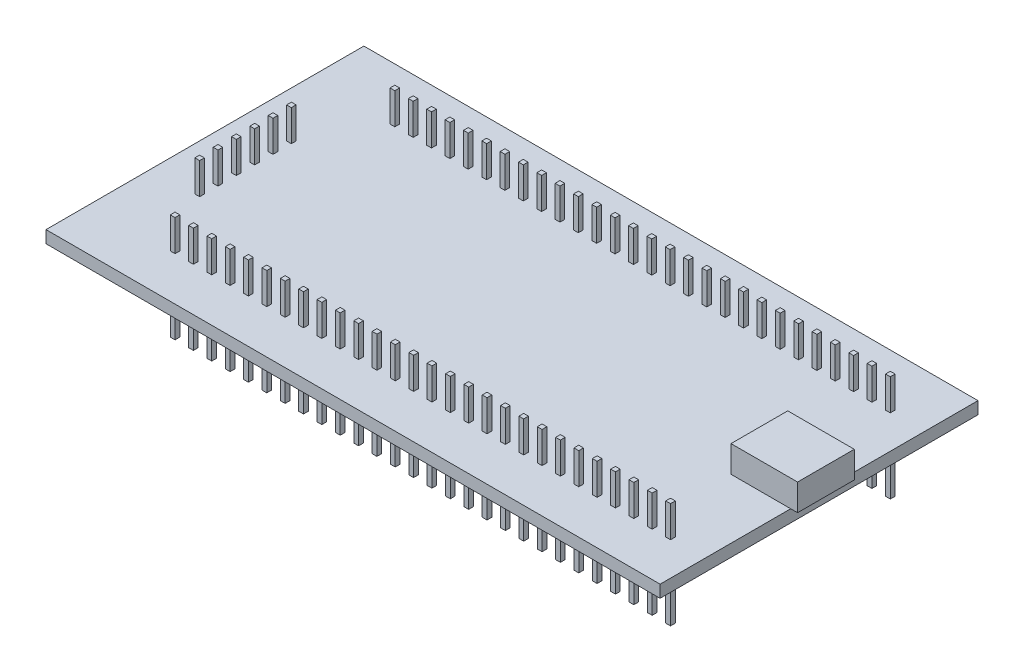
SolidWorks part; units mm, degrees
note: The reader was unsure of these and kept them because the rebuilt part matched: shared geometry of "Sketch3<4>", "Sketch4<6>".
ref_plane "Front Plane" through (0, 0, 0) normal (0, 0, 1) x (1, 0, 0)
ref_plane "Top Plane" through (0, 0, 0) normal (0, 1, 0) x (1, 0, 0)
ref_plane "Right Plane" through (0, 0, 0) normal (1, 0, 0) x (0, 0, -1)
sketch "Sketch1" plane through (0, 0, 0) normal (0, 1, 0) x (1, 0, 0)
  line L1 (0, 0) -> (85, 0)
  line L2 (0, 0) -> (0, -44)
  line L3 (0, -44) -> (85, -44)
  line L4 (85, 0) -> (85, -44)
  dimension "D1" = 85
  dimension "D2" = 44
extrude "Board" add sketch "Sketch1" along normal blind 1.7 contours L1 L4 L3 L2
sketch "Sketch2" plane through (0, 1.7, 0) normal (0, 1, 0) x (1, 0, 0)
  line L0 (0, -22) -> (85, -22) construction
  line L1 (76.74, -18.075) -> (85.95, -18.075)
  line L2 (76.74, -18.075) -> (76.74, -25.925)
  line L3 (76.74, -25.925) -> (85.95, -25.925)
  line L4 (85.95, -18.075) -> (85.95, -25.925)
  line L5 (0, 0) -> (0, -44) construction
  line L6 (85, 0) -> (85, -44) construction
  dimension "D1" = 9.21
  dimension "D2" = 7.85
  dimension "D3" = 0.95
extrude "USB" add sketch "Sketch2" along normal blind 3.68 separate body
sketch "Sketch4" plane through (0, 1.7, -1.7) normal (0, -1, 0) x (1, 0, 0)
  line L1 (6.03, 18.43) -> (6.69, 18.43)
  line L2 (6.03, 18.43) -> (6.03, 17.77)
  line L3 (6.03, 17.77) -> (6.69, 17.77)
  line L4 (6.69, 18.43) -> (6.69, 17.77)
  line L6 (6.03, 18.1) -> (6.69, 18.1) construction
  line L7 (5.09, 19.37) -> (7.63, 19.37)
  line L8 (5.09, 19.37) -> (5.09, 16.83)
  line L9 (5.09, 16.83) -> (7.63, 16.83)
  line L10 (7.63, 19.37) -> (7.63, 16.83)
  line L11 (6.36, 17.77) -> (6.36, 18.43) construction
  line L13 (0, 1.7) -> (0, 45.7) construction
  line L14 (0, 1.7) -> (85, 1.7) construction
  point P6 (70.6859, -18.9431)
  point P7 (6.9485, 16.7875)
  dimension "D1" = 0.66
  dimension "D2" = 5.09
  dimension "D3" = 15.13
  dimension "D4" = 2.54
sketch "Sketch3" plane through (0, 1.7, 0) normal (0, 1, 0) x (1, 0, 0)
  line L1 (79.74, -37.3) -> (80.4, -37.3)
  line L2 (79.74, -37.3) -> (79.74, -37.96)
  line L3 (79.74, -37.96) -> (80.4, -37.96)
  line L4 (80.4, -37.3) -> (80.4, -37.96)
  line L6 (79.74, -37.63) -> (80.4, -37.63) construction
  line L7 (78.8, -36.36) -> (81.34, -36.36)
  line L8 (78.8, -36.36) -> (78.8, -38.9)
  line L9 (78.8, -38.9) -> (81.34, -38.9)
  line L10 (81.34, -36.36) -> (81.34, -38.9)
  line L11 (80.07, -37.96) -> (80.07, -37.3) construction
  line L12 (85, 0) -> (85, -44) construction
  line L13 (0, -44) -> (85, -44) construction
  dimension "D1" = 0.66
  dimension "D2" = 3.66
  dimension "D3" = 5.1
  dimension "D4" = 2.54
extrude "SinglePin" add sketch "Sketch3" along normal blind 4.33 and the other way blind 10.33 separate body contours L4 L1 L2 L3
extrude "Boss-Extrude4" add sketch "Sketch3<4>" against normal blind 2.54 from surface at -1.7 separate body starting at face at (42.5, 0, 22)
sketch "Sketch3<4>" plane through (0, 1.7, 0) normal (0, 1, 0) x (1, 0, 0) same geometry as "Sketch3"
pattern_linear "LPattern1" count 28 spacing 2.54 along (-1, 0, 0) of "SinglePin", "Boss-Extrude4"
ref_plane "Plane1" through (0, 0, 22.42) normal (0, 0, 1) x (1, 0, 0)
mirror "Mirror1" about plane through (0, 0, 22.42) normal (0, 0, 1) of "LPattern1", "SinglePin", "Boss-Extrude4"
extrude "Boss-Extrude5" add sketch "Sketch4" along normal blind 2.54 from surface at 1.7 separate body contours L7 L10 L9 L8 starting at face at (42.5, 0, 22)
extrude "Boss-Extrude6" add sketch "Sketch4<6>" against normal up to vertex (4.33 mm away) and the other way up to vertex (10.33 mm away) separate body contours L1 L4 L3 L2 up to point (11.16, 6.03, 37.3) other way up to point (11.16, -8.63, 37.96)
sketch "Sketch4<6>" plane through (0, 1.7, -1.7) normal (0, -1, 0) x (1, 0, 0) same geometry as "Sketch4"
pattern_linear "LPattern2" count 6 spacing 2.54 along (0, 0, 1) of "Boss-Extrude5", "Boss-Extrude6"
